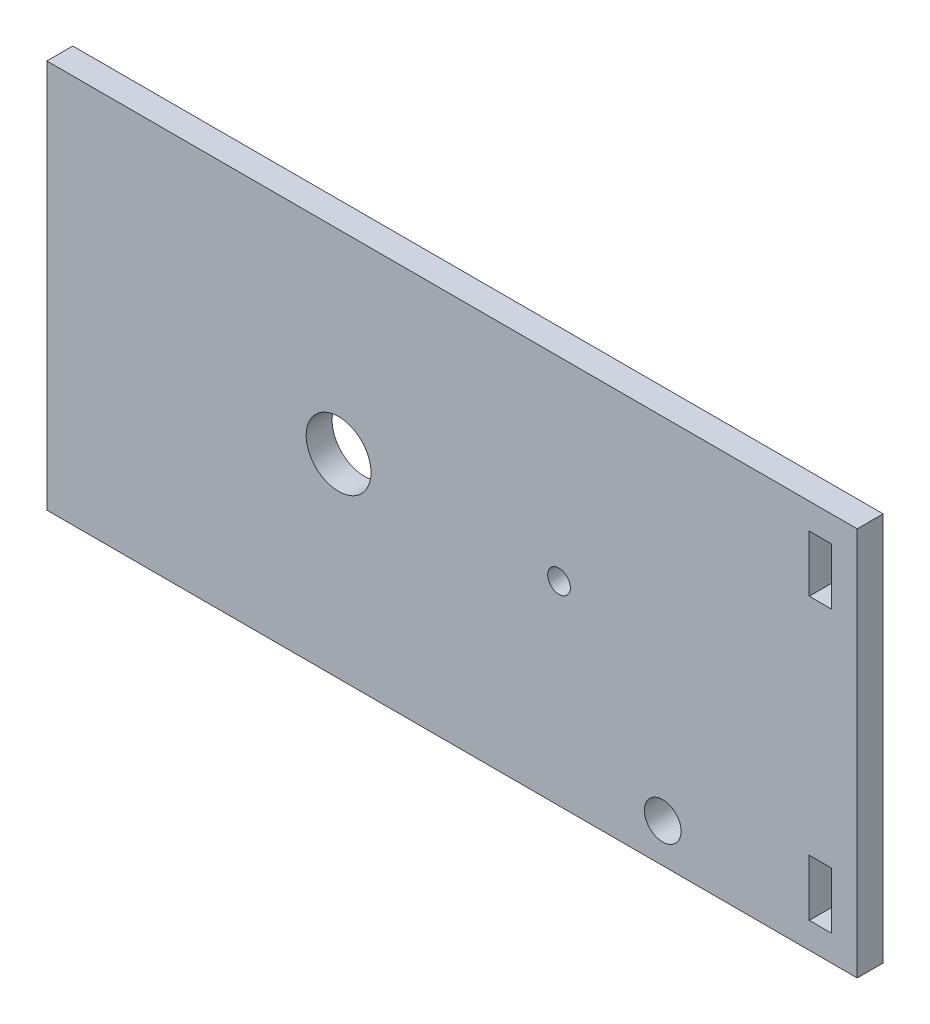
SolidWorks part; units mm, degrees
ref_plane "Front Plane" through (0, 0, 0) normal (0, 0, 1) x (1, 0, 0)
ref_plane "Top Plane" through (0, 0, 0) normal (0, 1, 0) x (1, 0, 0)
ref_plane "Right Plane" through (0, 0, 0) normal (1, 0, 0) x (0, 0, -1)
sketch "Sketch1" plane through (0, 0, 0) normal (0, 0, 1) x (1, 0, 0)
  line L1 (-81, -30) -> (40, -30)
  line L2 (-81, -30) -> (-81, 30)
  line L3 (-81, 30) -> (40, 30)
  line L11 (40, 30) -> (40, -30)
  circle A3 centre (-36, 0) radius 5
  circle A4 centre (14, -24) radius 2.83
  point P9 (-81, 0)
  dimension "D3" = 121
  dimension "D4" = 5.66
  dimension "D5" = 6
  dimension "D6" = 10
  dimension "D7" = 95
  dimension "D8" = 76
  dimension "D2" = 60
  dimension "D10" = 0
  dimension "D11" = 45
extrude "Boss-Extrude1" add sketch "Sketch1" along normal blind 4
sketch "Sketch2" plane through (0, 0, 0) normal (0, 0, 1) x (1, 0, 0)
  line L0 (40, -30) -> (44, -30)
  line L1 (44, -30) -> (44, 30)
  line L2 (44, 30) -> (40, 30)
  line L4 (40, 30) -> (-81, 30) construction
  line L16 (40, 30) -> (40, -30)
  dimension "D1" = 4
extrude "Boss-Extrude2" add sketch "Sketch2" along normal blind 4
sketch "Sketch3" plane through (0, 0, 0) normal (0, 0, 1) x (1, 0, 0)
  line L0 (40, 30) -> (40, -30) construction
  line L1 (40, 26) -> (36.6, 26)
  line L2 (40, 26) -> (40, 17.3)
  line L3 (40, 17.3) -> (36.6, 17.3)
  line L4 (36.6, 26) -> (36.6, 17.3)
  line L5 (-81, -30) -> (40, -30) construction
  line L6 (40, -17.3) -> (36.6, -17.3)
  line L7 (40, -17.3) -> (40, -26)
  line L8 (40, -26) -> (36.6, -26)
  line L9 (36.6, -17.3) -> (36.6, -26)
  line L10 (-81, 30) -> (40, 30) construction
  circle A0 centre (-2, 0) radius 1.75
  circle A1 centre (-36, 0) radius 5 construction
  dimension "D1" = 3.5
  dimension "D2" = 34
  dimension "D3" = 4
  dimension "D4" = 4
  dimension "D5" = 3.4
  dimension "D6" = 8.7
extrude "Cut-Extrude1" cut sketch "Sketch3" along normal through all both and the other way through all
equation "\"hole_width\"=3.4"
equation "\"D5@Sketch3\"=\"hole_width\""
equation "\"hole_length\"=8.7"
equation "\"D6@Sketch3\"=\"hole_length\""
